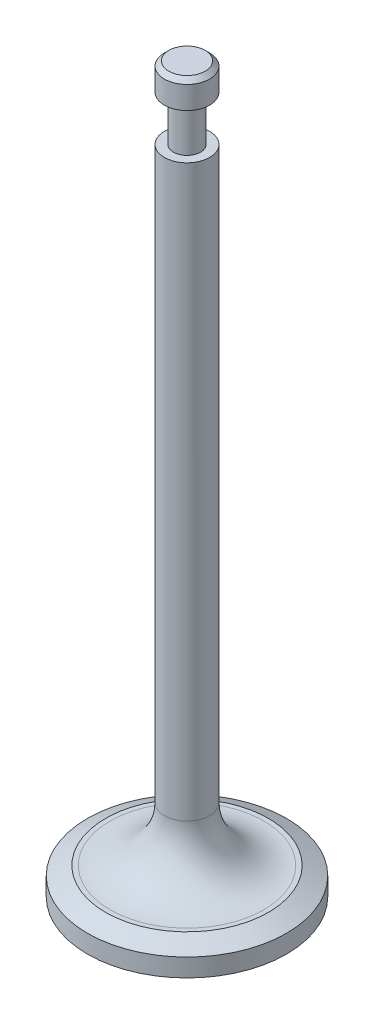
SolidWorks part; units mm, degrees
material "Gray Cast Iron"
ref_plane "Front Plane" through (0, 0, 0) normal (0, 0, 1) x (1, 0, 0)
ref_plane "Top Plane" through (0, 0, 0) normal (0, 1, 0) x (1, 0, 0)
ref_plane "Right Plane" through (0, 0, 0) normal (1, 0, 0) x (0, 0, -1)
sketch "Sketch2" plane through (0, 0, 0) normal (0, 0, 1) x (1, 0, 0)
  line L0 (0, 0) -> (0, 80)
  line L1 (0, 80) -> (2.5, 80)
  line L2 (2.5, 80) -> (2.5, 77)
  line L3 (2.5, 77) -> (1.5, 77)
  line L4 (1.5, 77) -> (1.5, 72)
  line L5 (1.5, 72) -> (2.5, 72)
  line L6 (2.5, 72) -> (2.5, 3)
  line L7 (2.5, 3) -> (11, 3)
  line L8 (11, 3) -> (11, 0)
  line L9 (11, 0) -> (0, 0)
  dimension "D1" = 1
  dimension "D2" = 80
  dimension "D3" = 3
  dimension "D4" = 11
  dimension "D5" = 3
  dimension "D6" = 2.5
  dimension "D7" = 5
revolve "Revolve1" add sketch "Sketch2" angle 360 about L0
fillet "Fillet1" radius 6 1 edges at (0, 3, -2.5)
chamfer "Chamfer1" distance 0.5 angle 45 1 edges at (0, 80, -2.5)
chamfer "Chamfer2" distance 2 distance2 1 1 edges at (0, 3, -11) first distance on face at (0, 3, 8.5)
